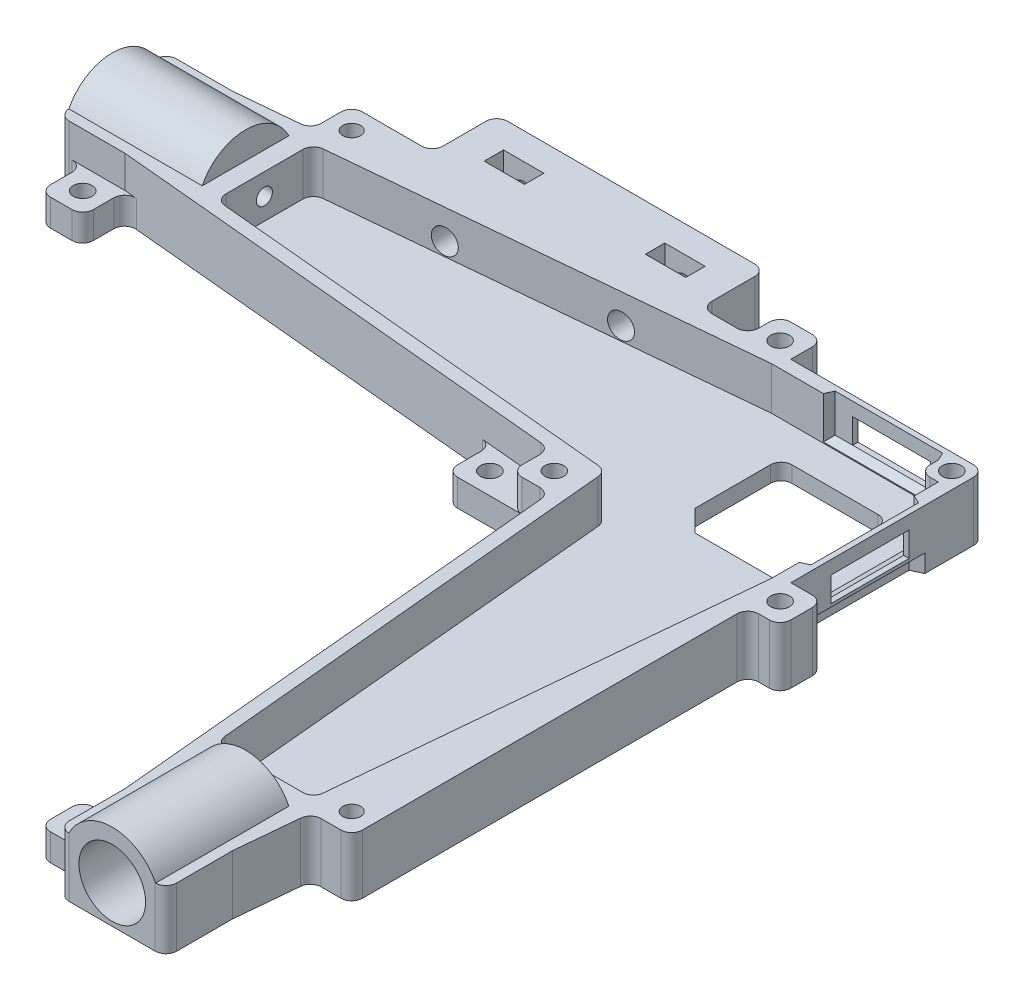
SolidWorks part; units mm, degrees
ref_plane "Front Plane" through (0, 0, 0) normal (0, 0, 1) x (1, 0, 0)
ref_plane "Top Plane" through (0, 0, 0) normal (0, 1, 0) x (1, 0, 0)
ref_plane "Right Plane" through (0, 0, 0) normal (1, 0, 0) x (0, 0, -1)
sketch "x Sensor" plane through (0, 0, 0) normal (0, 0, 1) x (1, 0, 0)
  line L0 (-13, 0) -> (0, 0) construction
  line L1 (-22.5, 1.5) -> (-13, 1.5)
  line L2 (-22.5, 1.5) -> (-22.5, -1.5)
  line L3 (-22.5, -1.5) -> (-13, -1.5)
  line L4 (-13, 1.5) -> (-13, -1.5)
  point P4 (-13, 0)
  dimension "D1" = 13
  dimension "D2" = 3
  dimension "D3" = 9.5
sketch "y Sensor" plane through (0, 0, 0) normal (1, 0, 0) x (0, 0, -1)
  line L0 (-13, 0) -> (0, 0) construction
  line L1 (-13, 1.5) -> (-22.5, 1.5)
  line L2 (-13, 1.5) -> (-13, -1.5)
  line L3 (-13, -1.5) -> (-22.5, -1.5)
  line L4 (-22.5, 1.5) -> (-22.5, -1.5)
  line L5 (0, 1.5) -> (0, -1.5) construction
  dimension "D1" = 9.5
  dimension "D2" = 13
ref_plane "y LED plane" through (-130, 0, 0) normal (1, 0, 0) x (0, 0, -1)
ref_plane "x LED plane" through (0, 0, 130) normal (0, 0, 1) x (1, 0, 0)
sketch "y LED" plane through (-130, 0, 0) normal (1, 0, 0) x (0, 0, -1)
  line L0 (-17.75, 1.5) -> (-17.75, -1.5) construction
  line L1 (-13, 1.5) -> (-22.5, 1.5) construction
  line L2 (-13, -1.5) -> (-22.5, -1.5) construction
  line L3 (-25.25, 0) -> (-10.25, 0) construction
  line L4 (-13, 0) -> (0, 0) construction
  point P10 (-17.75, 0)
  point P11 (-17.75, 0)
  dimension "D1" = 15
sketch "x LED" plane through (0, 0, 130) normal (0, 0, 1) x (1, 0, 0)
  line L0 (-17.75, 1.5) -> (-17.75, -1.5) construction
  line L1 (-22.5, 1.5) -> (-13, 1.5) construction
  line L2 (-22.5, -1.5) -> (-13, -1.5) construction
  line L3 (-25.25, 0) -> (-10.25, 0) construction
  point P9 (-17.75, 0)
  point P10 (-17.75, 0)
  dimension "D1" = 15
ref_plane "y LED cross-plane" through (0, 0, 17.75) normal (0, 0, 1) x (0, -1, 0)
ref_plane "x LED cross-plane" through (-17.75, 0, 0) normal (1, 0, 0) x (0, -1, 0)
ref_plane "Floor plane" through (0, -4, 0) normal (0, 1, 0) x (1, 0, 0)
ref_plane "Ceiling plane" through (0, 4, 0) normal (0, 1, 0) x (1, 0, 0)
sketch "Sketch10" plane through (0, -4, 0) normal (0, 1, 0) x (1, 0, 0)
  line L0 (0, 0) -> (-20, 0)
  line L1 (-20, 0) -> (-130, -10.25)
  line L2 (-130, -25.25) -> (-130, -10.25) construction
  line L3 (-130, -10.25) -> (-140, -10.25)
  line L4 (-140, -10.25) -> (-140, -25.25) construction
  line L5 (-140, -25.25) -> (-130, -25.25)
  line L6 (-130, -25.25) -> (-34.1788, -34.1788)
  line L7 (-20, -35.5) -> (-130, -25.25) construction
  line L8 (-34.1788, -34.1788) -> (-25.25, -130)
  line L9 (-25.25, -130) -> (-10.25, -130) construction
  line L10 (-25.25, -130) -> (-25.25, -140)
  line L11 (-25.25, -140) -> (-10.25, -140) construction
  line L12 (-10.25, -140) -> (-10.25, -130)
  line L13 (-10.25, -130) -> (0, -20)
  line L14 (0, -20) -> (0, 0)
  line L15 (-140, -17.75) -> (-51.5337, -17.75) construction
  line L16 (-17.75, -140) -> (-17.75, -69.9842) construction
  line L17 (-20.1162, 2.5) -> (-130.1162, -7.75)
  line L18 (-130.1162, -7.75) -> (-142.5, -7.75)
  line L19 (-142.5, -7.75) -> (-142.5, -10.25)
  line L20 (-142.5, -27.75) -> (-130.1162, -27.75)
  line L21 (-130.1162, -27.75) -> (-36.4756, -36.4756)
  line L23 (-36.4756, -36.4756) -> (-27.75, -130.1162)
  line L24 (-27.75, -130.1162) -> (-27.75, -142.5)
  line L25 (-27.75, -142.5) -> (-25.25, -142.5)
  line L26 (-7.75, -142.5) -> (-7.75, -130.1162)
  line L27 (-7.75, -130.1162) -> (2.5, -20.1162)
  line L28 (2.5, -20.1162) -> (2.5, 2.5)
  line L29 (2.5, 2.5) -> (-20.1162, 2.5)
  line L30 (-140, -10.25) -> (-142.5, -10.25)
  line L31 (-140, -25.25) -> (-142.5, -25.25)
  line L32 (-142.5, -10.25) -> (-142.5, -25.25) construction
  line L33 (-142.5, -7.75) -> (-142.5, -27.75) construction
  line L34 (-142.5, -25.25) -> (-142.5, -27.75)
  line L35 (-25.25, -140) -> (-25.25, -142.5)
  line L36 (-10.25, -140) -> (-10.25, -142.5)
  line L37 (-25.25, -142.5) -> (-10.25, -142.5) construction
  line L38 (-27.75, -142.5) -> (-7.75, -142.5) construction
  line L39 (-10.25, -142.5) -> (-7.75, -142.5)
  line L40 (-15.4308, -35.9258) -> (-34.1788, -34.1788) construction
  line L41 (-36.4756, -36.4756) -> (-36.4756, -36.4756) construction
  line L42 (-25.25, -130) -> (-35.5, -20) construction
  line L43 (-130.1162, -27.75) -> (-36.4756, -36.4756) construction
  line L44 (-130, -25.25) -> (-15.4308, -35.9258) construction
  dimension "D2" = 20
  dimension "D3" = 10
  dimension "D4" = 2.5
sketch "Max Shadows" plane through (0, 0, 0) normal (0, 1, 0) x (1, 0, 0)
  line L0 (-130, -17.75) -> (0, -13) construction
  line L1 (0, -13) -> (0, -22.5) construction
  line L2 (0, -22.5) -> (-130, -17.75) construction
  line L3 (0, -20) -> (0, 0) construction
  line L4 (-17.75, -130) -> (-22.5, 0) construction
  line L5 (-25.25, -130) -> (-10.25, -130) construction
  line L6 (-22.5, 0) -> (-13, 0) construction
  line L7 (0, 0) -> (-20, 0) construction
  line L8 (-17.75, -130) -> (-13, 0) construction
extrude "Boss-Extrude3" add sketch "Sketch10" along normal up to surface (8 mm away) up to plane "Ceiling plane"
sketch "Sketch12" plane through (0, -4, 0) normal (0, 1, 0) x (1, 0, 0)
  line L0 (-142.5, -10.25) -> (-142.5, -25.25) construction
  line L1 (-142.5, -7.75) -> (-142.5, -10.25) construction
  line L2 (-130.1162, -7.75) -> (-142.5, -7.75) construction
  line L3 (-20.1162, 2.5) -> (-130.1162, -7.75) construction
  line L4 (2.5, 2.5) -> (-20.1162, 2.5) construction
  line L5 (2.5, -20.1162) -> (2.5, 2.5) construction
  line L6 (-7.75, -130.1162) -> (2.5, -20.1162) construction
  line L7 (-7.75, -142.5) -> (-7.75, -130.1162) construction
  line L8 (-10.25, -142.5) -> (-7.75, -142.5) construction
  line L9 (-25.25, -142.5) -> (-10.25, -142.5) construction
  line L10 (-27.75, -142.5) -> (-25.25, -142.5) construction
  line L11 (-27.75, -130.1162) -> (-27.75, -142.5) construction
  line L12 (-36.4756, -36.4756) -> (-27.75, -130.1162) construction
  line L13 (-142.5, -25.25) -> (-142.5, -27.75) construction
  line L14 (-142.5, -27.75) -> (-130.1162, -27.75) construction
  line L15 (-130.1162, -27.75) -> (-36.4756, -36.4756) construction
  line L17 (-142.5, -10.25) -> (-142.5, -25.25)
  line L18 (-142.5, -7.75) -> (-142.5, -10.25)
  line L19 (-130.1162, -7.75) -> (-142.5, -7.75)
  line L20 (-20.1162, 2.5) -> (-130.1162, -7.75)
  line L21 (2.5, 2.5) -> (-20.1162, 2.5)
  line L22 (2.5, -20.1162) -> (2.5, 2.5)
  line L23 (-7.75, -130.1162) -> (2.5, -20.1162)
  line L24 (-7.75, -142.5) -> (-7.75, -130.1162)
  line L25 (-10.25, -142.5) -> (-7.75, -142.5)
  line L26 (-25.25, -142.5) -> (-10.25, -142.5)
  line L27 (-27.75, -142.5) -> (-25.25, -142.5)
  line L28 (-27.75, -130.1162) -> (-27.75, -142.5)
  line L29 (-36.4756, -36.4756) -> (-27.75, -130.1162)
  line L30 (-142.5, -25.25) -> (-142.5, -27.75)
  line L31 (-142.5, -27.75) -> (-130.1162, -27.75)
  line L32 (-130.1162, -27.75) -> (-36.4756, -36.4756)
extrude "Boss-Extrude4" add sketch "Sketch12" against normal blind 3
sketch "Sketch13" plane through (0, 0, 17.75) normal (0, 0, 1) x (0, -1, 0)
  line L0 (-4, -130) -> (-0.15, -130)
  line L1 (4, -130) -> (4, -134.05)
  line L2 (4, -142.5) -> (4, -130) construction
  line L3 (-4, -130) -> (4, -130) construction
  line L5 (0.15, -130) -> (4, -130)
  line L6 (-0.15, -130) -> (0.15, -130) construction
  line L8 (-0.15, -130) -> (-0.15, -130.2)
  line L9 (-4, -130) -> (-4, -140)
  line L10 (-4, -142.5) -> (-4, -130) construction
  line L11 (-4, -140) -> (4, -140)
  line L12 (4, -140) -> (4, -136.5)
  line L13 (4, -136.5) -> (-3, -136.5)
  line L14 (-3, -136.5) -> (-3, -133.05)
  line L15 (-0.15, -130.2) -> (-3, -133.05)
  line L16 (0, -130) -> (0, -136.5) construction
  line L17 (-2.5, -140) -> (-2.5, -136.5) construction
  line L18 (-2.5, -136.5) -> (-2.5, -135.2) construction
  line L19 (2.5, -140) -> (2.5, -136.5) construction
  line L20 (2.5, -136.5) -> (2.5, -135.2) construction
  line L21 (0.15, -130) -> (0.15, -130.2)
  line L22 (0.15, -130.2) -> (4, -134.05)
  arc A0 (-2.5, -135.2) -> (2.5, -135.2) centre (0, -135.2) cw construction
  point P13 (0, -130)
  point P26 (0, -132.7)
  dimension "D3" = 7.3
  dimension "D1" = 0.3
  dimension "D2" = 1
  dimension "D4" = 5
  dimension "D5" = 45
  dimension "D6" = 6.5
  dimension "D7" = 10
  dimension "D8" = 0.2
extrude "Boss-Extrude5" [suppressed] add sketch "Sketch13" along normal up to next and the other way up to next
sketch "Sketch14" [suppressed] plane through (-140, 0, 0) normal (-1, 0, 0) x (0, 0, 1)
  line L0 (17.75, 1.5) -> (17.75, -1.5) construction
  circle A0 centre (17.75, 0) radius 6.2
  dimension "D1" = 12.4
extrude "Cut-Extrude1" [suppressed] cut sketch "Sketch14" against normal up to next
sketch "Sketch38" [suppressed] plane through (-140, 0, 0) normal (-1, 0, 0) x (0, 0, 1)
  line L0 (17.75, 2.5) -> (17.75, -2.5) construction
  line L1 (16.45, 2.5) -> (19.05, 2.5)
  line L2 (16.45, 2.5) -> (16.45, -2.5)
  line L3 (16.45, -2.5) -> (19.05, -2.5)
  line L4 (19.05, 2.5) -> (19.05, -2.5)
  point P6 (17.75, 0)
  dimension "D1" = 5
  dimension "D2" = 2.6
extrude "Cut-Extrude20" [suppressed] cut sketch "Sketch38" against normal blind 2.3
sketch "Sketch15" plane through (-17.75, 0, 0) normal (1, 0, 0) x (0, -1, 0)
  line L0 (-4, -130) -> (-0.15, -130)
  line L1 (4, -130) -> (4, -134.05)
  line L5 (0.15, -130) -> (4, -130)
  line L6 (-0.15, -130) -> (0.15, -130) construction
  line L8 (-0.15, -130) -> (-0.15, -130.2)
  line L9 (-4, -130) -> (-4, -140)
  line L11 (-4, -140) -> (4, -140)
  line L12 (4, -140) -> (4, -136.5)
  line L13 (4, -136.5) -> (-3, -136.5)
  line L14 (-3, -136.5) -> (-3, -133.05)
  line L15 (-0.15, -130.2) -> (-3, -133.05)
  line L16 (0, -130) -> (0, -136.5) construction
  line L17 (-2.5, -140) -> (-2.5, -136.5) construction
  line L18 (-2.5, -136.5) -> (-2.5, -135.2) construction
  line L19 (2.5, -140) -> (2.5, -136.5) construction
  line L20 (2.5, -136.5) -> (2.5, -135.2) construction
  line L21 (0.15, -130) -> (0.15, -130.2)
  line L22 (0.15, -130.2) -> (4, -134.05)
  arc A0 (-2.5, -135.2) -> (2.5, -135.2) centre (0, -135.2) cw construction
extrude "Boss-Extrude6" [suppressed] add sketch "Sketch15" along normal up to next and the other way up to next
sketch "Sketch16" [suppressed] plane through (0, 0, 140) normal (0, 0, -1) x (-1, 0, 0)
  circle A0 centre (17.75, 0) radius 6.2
extrude "Cut-Extrude2" [suppressed] cut sketch "Sketch16" along normal up to next
sketch "Sketch39" [suppressed] plane through (0, 0, 140) normal (0, 0, 1) x (1, 0, 0)
  line L1 (-16.45, 2.5) -> (-19.05, 2.5)
  line L2 (-16.45, 2.5) -> (-16.45, -2.5)
  line L3 (-16.45, -2.5) -> (-19.05, -2.5)
  line L4 (-19.05, 2.5) -> (-19.05, -2.5)
  line L5 (-16.45, 2.5) -> (-19.05, -2.5) construction
  line L6 (-16.45, -2.5) -> (-19.05, 2.5) construction
  point P0 (-17.75, 0)
  dimension "D1" = 2.6
  dimension "D2" = 5
extrude "Cut-Extrude21" [suppressed] cut sketch "Sketch39" against normal blind 2.3
sketch "Sketch18" plane through (0, 0, -2.5) normal (0, 0, -1) x (-1, 0, 0)
  line L0 (-2.5, -7) -> (20.1162, -7) construction
  line L1 (-2.5, 4) -> (130.1162, 4)
  line L2 (-2.5, 4) -> (-2.5, -7)
  line L3 (-2.5, -7) -> (130.1162, -7)
  line L4 (130.1162, 4) -> (130.1162, -7)
  line L6 (130.1162, 4) -> (130.1162, -7) construction
extrude "Cut-Extrude4" cut sketch "Sketch18" against normal offset from surface (1.5 mm away) 1 up to face at (-10, 0, 0)
sketch "Sketch20" plane through (2.5, 0, 0) normal (1, 0, 0) x (0, 0, -1)
  line L0 (-20.1162, 4) -> (1, 4) construction
  line L1 (1, -7) -> (-130.1162, -7)
  line L2 (1, -7) -> (1, 4)
  line L3 (1, 4) -> (-130.1162, 4)
  line L4 (-130.1162, -7) -> (-130.1162, 4)
  line L5 (-130.1162, 4) -> (-130.1162, -7) construction
extrude "Cut-Extrude6" cut sketch "Sketch20" against normal offset from surface (1.5 mm away) 1 contours L1 L4 L3 L2 up to face at (0, 0, 10)
sketch "Sketch21" plane through (0, 0, 0) normal (0, 0, 1) x (1, 0, 0)
  line L0 (-20, -4) -> (-46.9455, -4)
  line L1 (-46.9455, -4) -> (-46.9455, 4)
  line L2 (-46.9455, 4) -> (-20, 4)
  line L3 (-36.2138, 4) -> (-130.1162, 4) construction
  line L4 (0, 4) -> (-20, 4)
  line L6 (-20, -4) -> (0, -4)
  line L7 (0, -4) -> (0, 4)
  line L8 (0, 4) -> (-20, 4)
  line L10 (-20, -4) -> (0, -4)
  line L11 (0, -4) -> (0, 4)
  line L14 (-20, 4) -> (-20, -4)
  dimension "D1" = 0
extrude "Boss-Extrude7" add sketch "Sketch21" along normal offset from surface (1.5 mm away) 2.5 up to face at (-17.6069, -1.5, -1)
sketch "Sketch22" plane through (0, 0, 0) normal (-1, 0, 0) x (0, 0, 1)
  line L0 (20, -4) -> (46.9455, -4)
  line L1 (46.9455, -4) -> (46.9455, 4)
  line L2 (46.9455, 4) -> (20, 4)
  line L4 (20, -4) -> (20, 4)
  line L5 (1.5, -4) -> (20, -4)
  line L7 (20, 4) -> (1.5, 4)
  line L8 (1.5, 4) -> (1.5, -4)
  line L9 (1.5, -4) -> (20, -4)
  line L11 (20, 4) -> (1.5, 4)
  line L13 (1.5, 4) -> (1.5, -4)
  dimension "D1" = 0
extrude "Boss-Extrude8" add sketch "Sketch22" along normal offset from surface (1.5 mm away) 2.5 up to face at (1, -1.5, 17.6069)
sketch "Sketch17" plane through (0, 0, 0) normal (0, 0, 1) x (1, 0, 0)
  line L1 (-8, -3.1) -> (-22.5, -3.1)
  line L2 (-8, -3.1) -> (-8, 1.5)
  line L3 (-8, 1.5) -> (-22.5, 1.5)
  line L4 (-22.5, -3.1) -> (-22.5, 1.5)
  dimension "D1" = 14.5
  dimension "D2" = 4.6
extrude "Cut-Extrude3" cut sketch "Sketch17" against normal through all and the other way up to next
sketch "Sketch19" plane through (0, 0, 0) normal (1, 0, 0) x (0, 0, -1)
  line L1 (-13, -3.1) -> (-27.5, -3.1)
  line L2 (-13, -3.1) -> (-13, 1.5)
  line L3 (-13, 1.5) -> (-27.5, 1.5)
  line L4 (-27.5, -3.1) -> (-27.5, 1.5)
  dimension "D1" = 14.5
  dimension "D2" = 4.6
extrude "Cut-Extrude5" cut sketch "Sketch19" along normal through all and the other way up to next
sketch "Sketch23" plane through (-1.5, 0, 0) normal (-1, 0, 0) x (0, 0, 1)
  line L0 (27.5, -3.1) -> (13, -3.1) construction
  line L1 (10.25, 1.5) -> (30.25, 1.5)
  line L2 (10.25, 1.5) -> (10.25, -3.1)
  line L3 (10.25, -3.1) -> (30.25, -3.1)
  line L4 (30.25, 1.5) -> (30.25, -3.1)
  point P4 (20.25, -3.1)
  point P7 (20.25, -3.1)
  dimension "D1" = 20
extrude "Cut-Extrude7" cut sketch "Sketch23" against normal up to surface (1.5 mm away)
sketch "Sketch25" plane through (-36, 0, 1.5) normal (0, 0, 1) x (1, 0, 0)
  line L1 (10.25, 1.5) -> (30.25, 1.5)
  line L2 (10.25, 1.5) -> (10.25, -3.1)
  line L3 (10.25, -3.1) -> (30.25, -3.1)
  line L4 (30.25, 1.5) -> (30.25, -3.1)
extrude "Cut-Extrude9" cut sketch "Sketch25" against normal up to surface (1.5 mm away)
chamfer "Chamfer2" distance 1.5 angle 25 6 edges at (-1.5, -3.1, 20.25) (-1.5, -0.8, 30.25) (-1.5, -0.8, 10.25) (-15.75, -3.1, 1.5) (-5.75, -0.8, 1.5) (-25.75, -0.8, 1.5)
sketch "Sketch28" plane through (0, 0, -1) normal (0, 0, -1) x (-1, 0, 0)
  line L0 (-1, -7) -> (36.2138, -7) construction
  line L1 (24.5, -4.6) -> (6, -4.6)
  line L2 (24.5, -4.6) -> (24.5, -7)
  line L3 (24.5, -7) -> (6, -7)
  line L4 (6, -4.6) -> (6, -7)
  line L7 (22.5, -3.1) -> (8, -3.1) construction
  line L8 (8, -3.1) -> (8, 1.5) construction
  line L10 (22.5, 1.5) -> (22.5, -3.1) construction
  dimension "D1" = 1.5
  dimension "D2" = 2
  dimension "D3" = 2
extrude "Cut-Extrude10" cut sketch "Sketch28" against normal blind 2
sketch "Sketch29" plane through (1, 0, 5) normal (-1, 0, 0) x (0, 0, 1)
  line L0 (22.5, -3.1) -> (8, -3.1) construction
  line L1 (24.5, -4.6) -> (6, -4.6)
  line L2 (24.5, -4.6) -> (24.5, -7)
  line L3 (24.5, -7) -> (6, -7)
  line L4 (6, -4.6) -> (6, -7)
  line L5 (22.5, 1.5) -> (22.5, -3.1) construction
  line L6 (8, -3.1) -> (8, 1.5) construction
  line L7 (31.2138, -7) -> (-6, -7) construction
  dimension "D1" = 1.5
  dimension "D2" = 2
  dimension "D3" = 2
extrude "Cut-Extrude11" cut sketch "Sketch29" along normal blind 2
chamfer "Chamfer3" distance 2 angle 25 6 edges at (-24.5, -5.8, -1) (-15.25, -4.6, -1) (-6, -5.8, -1) (1, -5.8, 11) (1, -5.8, 29.5) (1, -4.6, 20.25)
sketch "Sketch30" plane through (0, -4, 0) normal (0, 1, 0) x (1, 0, 0)
  line L0 (-13.493, -13.493) -> (-21.7069, -21.7069) construction
  line L1 (-13.8037, -21.9956) -> (-21.9956, -13.8037) construction
  line L2 (-130, -17.75) -> (0, -13) construction
  line L3 (-17.75, -130) -> (-22.5, 0) construction
  line L4 (0, -22.5) -> (-130, -17.75) construction
  line L5 (-17.75, -130) -> (-13, 0) construction
  line L7 (-7.8997, -7.8997) -> (-27.8997, -7.8997)
  line L8 (-7.8997, -7.8997) -> (-7.8997, -27.8997)
  line L9 (-7.8997, -27.8997) -> (-27.8997, -27.8997)
  line L10 (-27.8997, -7.8997) -> (-27.8997, -27.8997)
  line L11 (-7.8997, -7.8997) -> (-27.8997, -27.8997) construction
  line L12 (-7.8997, -27.8997) -> (-27.8997, -7.8997) construction
  point P12 (-17.8997, -17.8997)
  point P13 (-17.8997, -17.8997)
  dimension "D1" = 20
extrude "Cut-Extrude12" cut sketch "Sketch30" against normal through all
fillet "Fillet1" radius 2 3 edges at (-7.8997, -5.5, 7.8997) (-7.8997, -5.5, 27.8997) (-27.8997, -5.5, 7.8997)
sketch "Sketch31" [suppressed] plane through (0, -0.15, 0) normal (0, 1, 0) x (1, 0, 0)
  line L0 (-130.2, -10.25) -> (-130.2, -25.25) construction
  line L1 (-130, -10.25) -> (-130.2, -10.25)
  line L2 (-130, -10.25) -> (-130, -15.25)
  line L3 (-130, -15.25) -> (-130.2, -15.25)
  line L4 (-130.2, -10.25) -> (-130.2, -15.25)
  line L6 (-130, -25.25) -> (-130.2, -25.25)
  line L7 (-130, -25.25) -> (-130, -20.25)
  line L8 (-130, -20.25) -> (-130.2, -20.25)
  line L9 (-130.2, -25.25) -> (-130.2, -20.25)
  dimension "D1" = 5
extrude "Boss-Extrude9" [suppressed] add sketch "Sketch31" along normal up to next
sketch "Sketch32" [suppressed] plane through (0, -0.15, 0) normal (0, 1, 0) x (1, 0, 0)
  line L0 (-25.25, -130.2) -> (-10.25, -130.2) construction
  line L1 (-25.25, -130) -> (-20.25, -130)
  line L2 (-25.25, -130) -> (-25.25, -130.2)
  line L3 (-25.25, -130.2) -> (-20.25, -130.2)
  line L4 (-20.25, -130) -> (-20.25, -130.2)
  line L6 (-10.25, -130) -> (-15.25, -130)
  line L7 (-10.25, -130) -> (-10.25, -130.2)
  line L8 (-10.25, -130.2) -> (-15.25, -130.2)
  line L9 (-15.25, -130) -> (-15.25, -130.2)
  dimension "D1" = 5
extrude "Boss-Extrude10" [suppressed] add sketch "Sketch32" along normal up to next
sketch "Sketch33" plane through (0, -7, 0) normal (0, -1, 0) x (1, 0, 0)
  line L0 (1, -1) -> (-36.4756, 36.4756) construction
  line L2 (-36.2138, -1) -> (-130.1162, 7.75) construction
  line L3 (-36.2138, -1) -> (-116.7016, -1)
  line L4 (-36.2138, -1) -> (-116.7016, 6.5)
  line L5 (1, 116.7016) -> (-6.5, 116.7016)
  line L6 (-116.7016, -1) -> (-116.7016, 6.5)
  line L7 (1, 36.2138) -> (-6.5, 116.7016)
  line L8 (1, 36.2138) -> (1, 116.7016)
  dimension "D1" = 7.5
extrude "Boss-Extrude11" add sketch "Sketch33" against normal up to surface (11 mm away) up to face at (-46.7448, 4, 46.7448)
sketch "Sketch35" plane through (0, 4, 0) normal (0, 1, 0) x (1, 0, 0)
  line L0 (1, 1) -> (-54.474, -54.474) construction
  line L2 (-116.7016, -6.5) -> (-116.7016, 1) construction
  line L3 (1, 1) -> (-116.7016, 1) construction
  circle A0 centre (-112.7016, -3) radius 1.65
  circle A1 centre (-3, -112.7016) radius 1.65
  dimension "D1" = 4
  dimension "D3" = 3.3
  dimension "D2" = 4
  dimension "D4" = 45
extrude "Cut-Extrude13" cut sketch "Sketch35" against normal through all
fillet "Fillet2" [suppressed] radius 2
chamfer "Chamfer4" [suppressed] distance 0.3 angle 45
chamfer "Chamfer5" distance 4 angle 45 1 edges at (-27.8997, -5.5, 27.8997)
fillet "Fillet3" [suppressed] radius 2
sketch "Sketch37" plane through (0, 1.5, 0) normal (0, -1, 0) x (1, 0, 0)
  line L0 (1, 27.5) -> (0, 27.5) construction
  line L1 (0, 27.5) -> (0, 30.25) construction
  line L2 (0, 30.25) -> (-1.5, 30.9495) construction
  line L3 (-1.5, 30.9495) -> (-1.5, 9.5505) construction
  line L4 (-1.5, 9.5505) -> (0, 10.25) construction
  line L5 (0, 10.25) -> (0, 13) construction
  line L6 (0, 13) -> (1, 13) construction
  line L7 (1, 13) -> (1, 27.5) construction
  line L8 (-25.75, 0) -> (-22.5, 0) construction
  line L9 (-22.5, 0) -> (-22.5, -1) construction
  line L10 (-22.5, -1) -> (-8, -1) construction
  line L11 (-8, -1) -> (-8, 0) construction
  line L12 (-8, 0) -> (-5.75, 0) construction
  line L13 (-5.75, 0) -> (-5.0505, 1.5) construction
  line L14 (-5.0505, 1.5) -> (-26.4495, 1.5) construction
  line L15 (-26.4495, 1.5) -> (-25.75, 0) construction
  line L16 (1, 27.5) -> (0, 27.5) construction
  line L17 (0, 27.5) -> (0, 30.25)
  line L18 (0, 30.25) -> (-1.5, 30.9495)
  line L19 (-1.5, 30.9495) -> (-1.5, 9.5505)
  line L20 (-1.5, 9.5505) -> (0, 10.25)
  line L21 (0, 10.25) -> (0, 13)
  line L22 (0, 13) -> (1, 13) construction
  line L23 (1, 13) -> (1, 27.5) construction
  line L24 (-25.75, 0) -> (-22.5, 0)
  line L25 (-22.5, 0) -> (-22.5, -1) construction
  line L26 (-22.5, -1) -> (-8, -1) construction
  line L27 (-8, -1) -> (-8, 0) construction
  line L28 (-8, 0) -> (-5.75, 0)
  line L29 (-5.75, 0) -> (-5.0505, 1.5)
  line L30 (-5.0505, 1.5) -> (-26.4495, 1.5)
  line L31 (-26.4495, 1.5) -> (-25.75, 0)
  line L32 (-22.5, 0) -> (-8, 0)
  line L33 (0, 13) -> (0, 27.5)
extrude "Cut-Extrude14" cut sketch "Sketch37" against normal through all
sketch "Sketch44" plane through (0, -4, 0) normal (0, 1, 0) x (1, 0, 0)
  line L0 (-114.2009, -8.7778) -> (-114.2009, -26.7222)
  line L1 (-130, -10.25) -> (-36.0976, -1.5) construction
  line L2 (-34.1788, -34.1788) -> (-130, -25.25) construction
  line L3 (-114.2009, -26.7222) -> (-130, -25.25)
  line L4 (-130, -25.25) -> (-142.5, -25.25)
  line L5 (-142.5, -25.25) -> (-142.5, -10.25)
  line L6 (-142.5, -10.25) -> (-130, -10.25)
  line L7 (-130, -10.25) -> (-114.2009, -8.7778)
  line L9 (-116.7016, -6.5) -> (-116.7016, -26.4892) construction
  line L10 (-116.7016, -12.9955) -> (-114.2009, -12.9955) construction
  line L11 (-136.3081, -7.75) -> (-136.25, -10.25) construction
  line L12 (-130.1162, -7.75) -> (-142.5, -7.75) construction
extrude "Boss-Extrude14" add sketch "Sketch44" along normal up to surface (8 mm away) up to face at (-72.1771, 4, 72.1771)
sketch "Sketch46" plane through (-142.5, 0, 0) normal (-1, 0, 0) x (0, 0, 1)
  line L0 (17.75, 0) -> (17.75, 9.8019) construction
  line L2 (7.75, 4) -> (27.75, 4) construction
  line L3 (9.6877, 4) -> (25.8123, 4)
  arc A0 (25.8123, 4) -> (9.6877, 4) centre (17.75, 0) ccw
  point P8 (17.75, 4)
  dimension "D1" = 9
extrude "Boss-Extrude15" add sketch "Sketch46" against normal offset from surface (24.7984 mm away) 1 up to face at (-116.7016, -1.5, 2.75)
sketch "Sketch41" plane through (-130, 0, 0) normal (1, 0, 0) x (0, 0, -1)
  circle A0 centre (-17.75, 0) radius 6.2
  dimension "D1" = 12.4
extrude "Cut-Extrude22" cut sketch "Sketch41" against normal through all and the other way blind 8.18
sketch "Sketch47" plane through (-130, 0, 0) normal (1, 0, 0) x (0, 0, -1)
  circle A0 centre (-17.75, 0) radius 1.5
  dimension "D1" = 3
extrude "Cut-Extrude24" cut sketch "Sketch47" along normal up to surface (15.7991 mm away) up to face at (-114.2009, 0, 17.75)
sketch "Sketch48" plane through (0, -4, 0) normal (0, 1, 0) x (1, 0, 0)
  line L0 (-25.25, -142.5) -> (-10.25, -142.5)
  line L1 (-10.25, -142.5) -> (-10.25, -130)
  line L2 (-10.25, -130) -> (-8.7778, -114.2009)
  line L3 (-1.5, -36.0976) -> (-10.25, -130) construction
  line L4 (-8.7778, -114.2009) -> (-26.7222, -114.2009)
  line L5 (-25.25, -130) -> (-34.1788, -34.1788) construction
  line L6 (-26.7222, -114.2009) -> (-25.25, -130)
  line L7 (-25.25, -130) -> (-25.25, -142.5)
  line L8 (-11.5803, -114.2009) -> (-11.5803, -116.7016) construction
  line L9 (-10.25, -136.25) -> (-7.75, -136.3081) construction
  line L10 (-7.75, -142.5) -> (-7.75, -130.1162) construction
  line L11 (1, -116.7016) -> (-6.5, -116.7016) construction
extrude "Boss-Extrude16" add sketch "Sketch48" along normal up to surface (8 mm away) up to face at (-51.3804, 4, 47.2052)
sketch "Sketch49" plane through (0, 0, 142.5) normal (0, 0, 1) x (1, 0, 0)
  line L0 (-27.75, 4) -> (-7.75, 4) construction
  line L1 (-17.75, 7.9098) -> (-17.75, 4) construction
  line L2 (-25.8123, 4) -> (-9.6877, 4)
  arc A0 (-25.8123, 4) -> (-9.6877, 4) centre (-17.75, 0) cw
  dimension "D1" = 9
extrude "Boss-Extrude17" add sketch "Sketch49" against normal offset from surface (24.7984 mm away) 1 up to face at (-2.75, -1.5, 116.7016)
sketch "Sketch51" plane through (0, 0, 130) normal (0, 0, 1) x (1, 0, 0)
  circle A0 centre (-17.75, 0) radius 6.2
  dimension "D1" = 12.4
extrude "Cut-Extrude25" cut sketch "Sketch51" along normal through all and the other way blind 8.18
sketch "Sketch52" plane through (0, 0, 130) normal (0, 0, 1) x (1, 0, 0)
  circle A0 centre (-17.75, 0) radius 1.5
  dimension "D1" = 3
extrude "Cut-Extrude26" cut sketch "Sketch52" against normal up to surface (15.7991 mm away) up to face at (-17.75, 0, 114.2009)
sketch "Sketch53" plane through (0, -7, 0) normal (0, -1, 0) x (1, 0, 0)
  line L0 (-101.7016, -1) -> (-101.7016, -13)
  line L1 (-25.4326, -1) -> (-116.7016, -1) construction
  line L2 (-101.7016, -13) -> (-51.7016, -13)
  line L3 (-51.7016, -13) -> (-51.7016, -1)
  line L4 (-116.7016, 6.5) -> (-116.7016, -1) construction
  line L5 (-51.7016, -1) -> (-101.7016, -1)
  dimension "D1" = 15
  dimension "D2" = 50
  dimension "D3" = 12
extrude "Boss-Extrude18" add sketch "Sketch53" against normal up to surface (11 mm away) up to face at (-67.3643, 4, 67.3643)
sketch "Sketch56" plane through (0, 0, -13) normal (0, 0, -1) x (-1, 0, 0)
  line L0 (76.7016, 4) -> (76.7016, -7) construction
  line L1 (101.7016, 4) -> (51.7016, 4) construction
  line L2 (101.7016, -7) -> (51.7016, -7) construction
  line L3 (51.7016, -1.5) -> (101.7016, -1.5) construction
  line L4 (51.7016, 4) -> (51.7016, -7) construction
  line L5 (101.7016, 4) -> (101.7016, -7) construction
  circle A0 centre (61.7016, -1.5) radius 2.3
  circle A1 centre (91.7016, -1.5) radius 2.3
  dimension "D1" = 30
  dimension "D2" = 4.6
extrude "Cut-Extrude27" cut sketch "Sketch56" against normal up to next
sketch "Sketch57" plane through (0, 0, -13) normal (0, 0, -1) x (-1, 0, 0)
  line L0 (76.7016, 4) -> (76.7016, -7) construction
  line L1 (101.7016, 4) -> (51.7016, 4) construction
  line L2 (101.7016, -7) -> (51.7016, -7) construction
  line L3 (57.9516, 0.6651) -> (57.9516, 4)
  line L4 (61.7016, -5.8301) -> (65.4516, -3.6651)
  line L5 (65.4516, -3.6651) -> (65.4516, 0.6651)
  line L6 (65.4516, 0.6651) -> (61.7016, 2.8301) construction
  line L7 (61.7016, 2.8301) -> (57.9516, 0.6651) construction
  line L8 (57.9516, 0.6651) -> (57.9516, -3.6651)
  line L9 (57.9516, -3.6651) -> (61.7016, -5.8301)
  line L10 (57.9516, 4) -> (65.4516, 4)
  line L11 (65.4516, 4) -> (65.4516, 0.6651)
  line L12 (91.7016, 2.8301) -> (95.4516, 0.6651) construction
  line L13 (87.9516, 0.6651) -> (91.7016, 2.8301) construction
  line L14 (87.9516, 4) -> (87.9516, 0.6651)
  line L15 (95.4516, 4) -> (87.9516, 4)
  line L16 (95.4516, -3.6651) -> (91.7016, -5.8301)
  line L17 (95.4516, 0.6651) -> (95.4516, -3.6651)
  line L18 (87.9516, -3.6651) -> (87.9516, 0.6651)
  line L19 (91.7016, -5.8301) -> (87.9516, -3.6651)
  line L20 (95.4516, 0.6651) -> (95.4516, 4)
  circle A0 centre (61.7016, -1.5) radius 3.75 construction
  circle A1 centre (91.7016, -1.5) radius 3.75 construction
  dimension "D1" = 7.5
extrude "Cut-Extrude28" cut sketch "Sketch57" against normal blind 3.6 from offset 5 offset against normal yes
sketch "Sketch58" plane through (0, -7, 0) normal (0, -1, 0) x (-1, 0, 0)
  line L0 (5.0505, -5.0505) -> (-1, 1) construction
  line L1 (-1, 1) -> (5.0505, 1)
  line L2 (-1, 1) -> (-1, -5.0505)
  line L3 (-1, -5.0505) -> (5.0505, -5.0505)
  line L4 (5.0505, 1) -> (5.0505, -5.0505)
  line L5 (2.0253, -2.0253) -> (77.3849, -2.0253) construction
  line L6 (2.0253, -2.0253) -> (2.0253, -72.6189) construction
  line L7 (39, -2.0253) -> (39, -39) construction
  line L8 (39, -39) -> (2.0253, -39) construction
  line L9 (39, -2.0253) -> (39, 3) construction
  line L10 (2.0253, -39) -> (-3, -39) construction
  line L11 (39, -39) -> (2.0253, -2.0253) construction
  line L12 (-1, 1) -> (51.7016, 1) construction
  line L13 (35, 7) -> (43, 7)
  line L14 (35, 7) -> (35, 1)
  line L15 (35, 1) -> (43, 1)
  line L16 (43, 7) -> (43, 1)
  line L17 (35, 7) -> (43, 1) construction
  line L18 (35, 1) -> (43, 7) construction
  line L19 (43, -35.8676) -> (36.4756, -36.4756)
  line L20 (130.1162, -27.75) -> (36.4756, -36.4756) construction
  line L21 (43, -35.8676) -> (43, -43)
  line L22 (-1, -35) -> (-1, -43)
  line L23 (-7, -35) -> (-1, -35)
  line L24 (-7, -35) -> (-7, -43)
  line L25 (-7, -43) -> (-1, -43)
  line L26 (35.8676, -43) -> (36.4756, -36.4756)
  line L27 (35.8676, -43) -> (43, -43)
  point P12 (39, 4)
  dimension "D1" = 4
  dimension "D2" = 4
  dimension "D3" = 6
  dimension "D4" = 42
extrude "Boss-Extrude19" add sketch "Sketch58" against normal up to surface (11 mm away) up to face at (-61.7016, 4, -6.2)
sketch "Sketch62" plane through (0, -7, 0) normal (0, -1, 0) x (1, 0, 0)
  line L0 (-43, 35.8676) -> (-43, 43)
  line L1 (-43, 43) -> (-55, 43)
  line L2 (-55, 43) -> (-55, 34.7495)
  line L3 (-130.1162, 27.75) -> (-43, 35.8676) construction
  line L4 (-55, 34.7495) -> (-43, 35.8676)
  line L5 (-138, 27.75) -> (-138, 35.75)
  line L6 (-142.5, 27.75) -> (-130.1162, 27.75) construction
  line L7 (-138, 35.75) -> (-130, 35.75)
  line L8 (-130, 35.75) -> (-130, 27.7608)
  line L9 (-130, 27.7608) -> (-130.1162, 27.75)
  line L10 (-130.1162, 27.75) -> (-138, 27.75)
  line L11 (1, -1) -> (-34.1788, 34.1788) construction
  line L12 (-27.75, 130.1162) -> (-27.75, 138)
  line L13 (-27.7608, 130) -> (-27.75, 130.1162)
  line L14 (-35.75, 130) -> (-27.7608, 130)
  line L15 (-35.75, 138) -> (-35.75, 130)
  line L16 (-27.75, 138) -> (-35.75, 138)
  point P14 (-49, 43)
  point P17 (-134, 35.75)
  dimension "D1" = 12
  dimension "D2" = 8
  dimension "D3" = 8
  dimension "D4" = 85
extrude "Boss-Extrude20" add sketch "Sketch62" against normal blind 5
sketch "Sketch64" plane through (0, -7, 0) normal (0, -1, 0) x (1, 0, 0)
  line L0 (-35.75, 134) -> (-24.8904, 134) construction
  line L1 (-35.75, 138) -> (-35.75, 130) construction
  line L2 (-51, 43) -> (-51, 33.7378) construction
  line L3 (-35.8676, 43) -> (-55, 43) construction
  line L5 (-134, 35.75) -> (-134, 25.1272) construction
  line L6 (-130, 35.75) -> (-138, 35.75) construction
  line L7 (-35.75, 138) -> (-35.75, 130) construction
  line L8 (-130, 35.75) -> (-138, 35.75) construction
  line L9 (-55, 43) -> (-55, 34.7495) construction
  circle A0 centre (-134, 31.75) radius 1.75
  circle A1 centre (-51, 39) radius 1.75
  circle A2 centre (-31.75, 134) radius 1.75
  point P4 (-31.75, 134)
  point P12 (-51, 39)
  point P17 (-134, 31.75)
  dimension "D5" = 3.5
  dimension "D1" = 83
  dimension "D2" = 95
  dimension "D3" = 4
  dimension "D4" = 4
  dimension "D6" = 4
extrude "Cut-Extrude31" cut sketch "Sketch64" against normal through all
fillet "Fillet4" radius 2 57 edges at (1, -1.5, -1) (-7.75, -1.5, 142.5) (-27.75, -1.5, 142.5) (-116.7016, -1.5, -1) (-116.7016, -1.5, 6.5) (-6.5, -1.5, 116.7016) (1, -1.5, 116.7016) (-142.5, -1.5, 27.75) (-142.5, -1.5, 7.75) (-114.2009, 0, 8.7778) (-114.2009, 0, 26.7222) (-142.5, 4, 26.7811) (-8.7778, 0, 114.2009) (-26.7222, 0, 114.2009) (-8.7189, 4, 142.5) (-101.7016, -1.5, -13) (-51.7016, -1.5, -13) (-5.0505, 0, 5.0505) (-35, -1.5, -7) (-43, -1.5, -1) (-43, -1.5, -7) (-35.8676, -1.5, 43) (-43, 1, 43) (-43, 1, 35.8676) (7, -1.5, 43) (7, -1.5, 35) (-55, -4.5, 34.7495) (-55, -4.5, 43) (-26.7811, 4, 142.5) (-130.1162, 1, 27.75) (-138, -4.5, 27.75) (-138, -4.5, 35.75) (-130, -4.5, 35.75) (-130, -4.5, 27.7608) (-27.75, 1, 130.1162) (-27.7608, -4.5, 130) (-35.75, -4.5, 130) (-35.75, -4.5, 138) (-27.75, -4.5, 138) (-34.1788, 0, 34.1788) (-142.5, 4, 8.7189)
sketch "Sketch59" plane through (0, -7, 0) normal (0, -1, 0) x (1, 0, 0)
  circle A0 centre (-39, -3) radius 1.75
  circle A1 centre (-39, 39) radius 1.75
  circle A2 centre (3, 39) radius 1.75
  circle A3 centre (-2.0253, 2.0253) radius 1.75
  dimension "D1" = 3.5
extrude "Cut-Extrude29" cut sketch "Sketch59" against normal through all
sketch "Sketch60" plane through (0, -7, 0) normal (0, -1, 0) x (1, 0, 0)
  line L0 (-116.7016, 4.6777) -> (-116.7016, 1) construction
  line L1 (-111.8648, -0.123) -> (-109.5786, 2.1632)
  line L2 (-109.5786, 2.1632) -> (-110.4154, 5.2862)
  line L3 (-110.4154, 5.2862) -> (-113.5384, 6.123)
  line L4 (-113.5384, 6.123) -> (-115.8246, 3.8368)
  line L5 (-115.8246, 3.8368) -> (-114.9878, 0.7138)
  line L6 (-114.9878, 0.7138) -> (-111.8648, -0.123)
  line L7 (-2.1632, 109.5786) -> (0.123, 111.8648)
  line L8 (0.123, 111.8648) -> (-0.7138, 114.9878)
  line L9 (-0.7138, 114.9878) -> (-3.8368, 115.8246)
  line L10 (-3.8368, 115.8246) -> (-6.123, 113.5384)
  line L11 (-6.123, 113.5384) -> (-5.2862, 110.4154)
  line L12 (-5.2862, 110.4154) -> (-2.1632, 109.5786)
  line L13 (-1, 116.7016) -> (-4.6777, 116.7016) construction
  circle A0 centre (-112.7016, 3) radius 2.8 construction
  circle A1 centre (-3, 112.7016) radius 2.8 construction
  dimension "D4" = 45
  dimension "D1" = 45
  dimension "D2" = 5.6
extrude "Cut-Extrude30" cut sketch "Sketch60" against normal blind 2.5 draft 5
equation "\"D1@Sketch39\"=\"D2@Sketch38\""
equation "\"D2@Sketch39\"=\"D1@Sketch38\""
equation "\"D1@Cut-Extrude21\"=\"D1@Cut-Extrude20\""
equation "\"D1@Sketch51\"=\"D1@Sketch41\""
equation "\"D2@Cut-Extrude25\"=\"D2@Cut-Extrude22\""
equation "\"D1@Sketch52\"=\"D1@Sketch47\""
